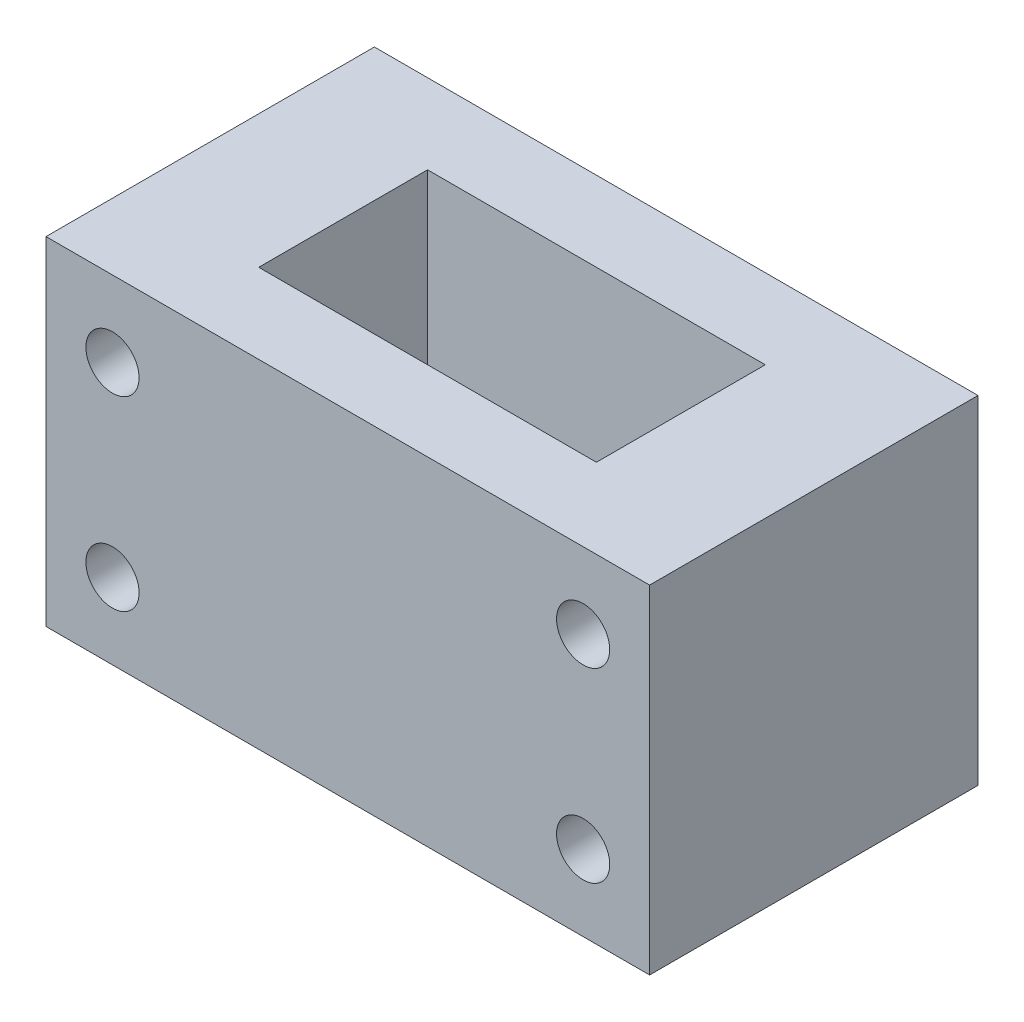
SolidWorks part; units mm, degrees
ref_plane "Front Plane" through (0, 0, 0) normal (0, 0, 1) x (1, 0, 0)
ref_plane "Top Plane" through (0, 0, 0) normal (0, 1, 0) x (1, 0, 0)
ref_plane "Right Plane" through (0, 0, 0) normal (1, 0, 0) x (0, 0, -1)
sketch "Sketch1" plane through (0, 0, 0) normal (0, 1, 0) x (1, 0, 0)
  line L1 (-22.7, 12.35) -> (22.7, 12.35)
  line L2 (-22.7, 12.35) -> (-22.7, -12.35)
  line L3 (-22.7, -12.35) -> (22.7, -12.35)
  line L4 (22.7, 12.35) -> (22.7, -12.35)
  line L5 (-22.7, 12.35) -> (22.7, -12.35) construction
  line L6 (-22.7, -12.35) -> (22.7, 12.35) construction
  line L7 (-12.7, -6.35) -> (12.7, -6.35)
  line L8 (-12.7, -6.35) -> (-12.7, 6.35)
  line L9 (-12.7, 6.35) -> (12.7, 6.35)
  line L10 (12.7, -6.35) -> (12.7, 6.35)
  line L11 (-12.7, -6.35) -> (12.7, 6.35) construction
  line L12 (-12.7, 6.35) -> (12.7, -6.35) construction
  point P0 (0, 0)
  point P7 (0, 0)
  dimension "D1" = 10
  dimension "D2" = 12.7
  dimension "D3" = 6
  dimension "D4" = 25.4
extrude "Boss-Extrude1" add sketch "Sketch1" along normal blind 25.4
sketch "Sketch2" plane through (0, 0, -12.35) normal (0, 0, -1) x (-1, 0, 0)
  line L0 (-22.7, 25.4) -> (-22.7, 0) construction
  line L1 (-22.7, 12.7) -> (22.7, 12.7) construction
  line L2 (22.7, 25.4) -> (22.7, 0) construction
  line L3 (0, 0) -> (0, 25.4) construction
  line L4 (-22.7, 25.4) -> (22.7, 25.4) construction
  circle A0 centre (-17.7, 5.7) radius 2
  circle A3 centre (-17.7, 19.7) radius 2
  circle A4 centre (17.7, 19.7) radius 2
  circle A5 centre (17.7, 5.7) radius 2
  dimension "D2" = 4
  dimension "D1" = 5
  dimension "D3" = 7
extrude "Cut-Extrude1" cut sketch "Sketch2" against normal through all
